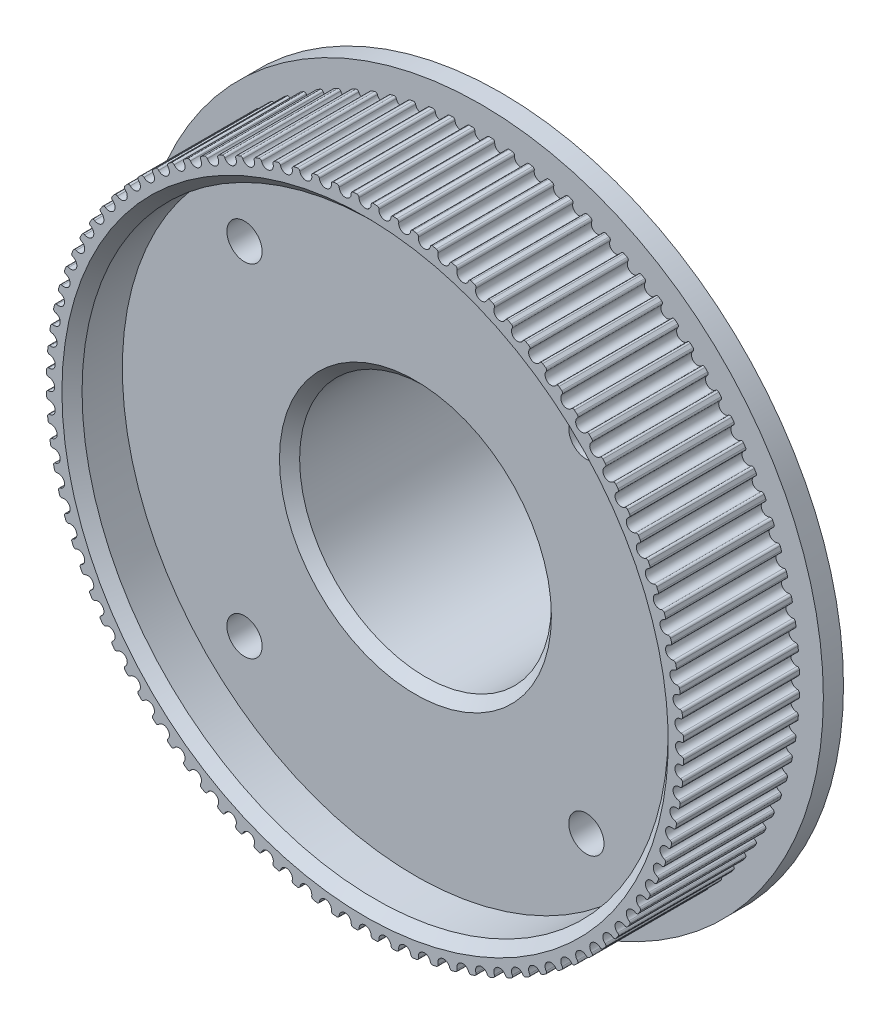
SolidWorks part; units mm, degrees
ref_plane "Спереди" through (0, 0, 0) normal (0, 0, 1) x (1, 0, 0)
ref_plane "Сверху" through (0, 0, 0) normal (0, 1, 0) x (1, 0, 0)
ref_plane "Справа" through (0, 0, 0) normal (1, 0, 0) x (0, 0, -1)
ref_axis "Ось1" through (0, 0, 55) along (0, 0, -1)
sketch "SketchRevolveGearBelt01" plane through (0, 0, 0) normal (1, 0, 0) x (0, 0, -1)
  line L0 (0, 0) -> (11.5, 0)
  line L1 (11.5, 0) -> (11.5, 31.6405)
  line L2 (11.5, 31.6405) -> (0, 31.6405)
  line L3 (0, 31.6405) -> (0, 0)
  dimension "GearBeltOutsideDiameter" = 31.6405
  dimension "D1" = 11.5
revolve "GearBelt01" add sketch "SketchRevolveGearBelt01" angle 360 about L0
sketch "SketchToothGearBelt01" plane through (0, 0, 0) normal (0, 0, 1) x (1, 0, 0)
  line L0 (-0.814, 31.63) -> (0, 34.1805)
  line L1 (0, 34.1805) -> (0.814, 31.63)
  arc A0 (0.814, 31.63) -> (0.6, 31.4215) centre (0.8086, 31.4215) ccw
  arc A1 (0.6, 31.4215) -> (-0.6, 31.4215) centre (0, 31.4215) cw
  arc A2 (-0.6, 31.4215) -> (-0.814, 31.63) centre (-0.8086, 31.4215) ccw
  dimension "GearBeltToothR1" = 0.4172
  dimension "GearBeltToothR2" = 1.2
  dimension "GearBeltToothCapX1" = 0.814
  dimension "GearBeltToothCapY1" = 2.5505
  dimension "GearBeltToothCapX2" = 0.814
  dimension "GearBeltToothCapY2" = 2.5505
extrude "ToothExtrudeCutGearBelt01" cut sketch "SketchToothGearBelt01" against normal blind 11.5
ref_axis "Ось2" through (34.8045, 0, 0) along (-1, 0, 0)
ref_plane "Плоскость1" through (0, 0, 0) normal (0, 0, -1) x (1, 0, 0)
pattern_circular "PatternGearBelt01" count 100 every 3.6 about axis through (0, 0, 55) along (0, 0, -1) of "ToothExtrudeCutGearBelt01"
sketch "Эскиз5" plane through (0, 0, -11.5) normal (0, 0, -1) x (-1, 0, 0)
  circle A0 centre (0, 0) radius 34
extrude "Бобышка-Вытянуть1" add sketch "Эскиз5" along normal blind 2
sketch "Эскиз6" plane through (0, 0, 0) normal (0, 0, 1) x (1, 0, 0)
  circle A0 centre (0, 0) radius 29.1
  dimension "D1" = 58.2
extrude "Вырез-Вытянуть2" cut sketch "Эскиз6" against normal blind 5
sketch "Эскиз7" plane through (0, 0, -13.5) normal (0, 0, -1) x (-1, 0, 0)
  circle A0 centre (0, 0) radius 20
  dimension "D1" = 40
extrude "Бобышка-Вытянуть2" add sketch "Эскиз7" along normal blind 2
sketch "Эскиз8" plane through (0, 0, -15.5) normal (0, 0, -1) x (-1, 0, 0)
  circle A0 centre (0, 0) radius 17.5
  dimension "D1" = 35
extrude "Бобышка-Вытянуть3" add sketch "Эскиз8" along normal blind 10
sketch "Эскиз9" plane through (0, 0, 0) normal (0, 0, 1) x (1, 0, 0)
  line L0 (0, 0) -> (16.9706, 16.9706) construction
  line L1 (0, 0) -> (10.5426, 0) construction
  circle A0 centre (0, 0) radius 24 construction
  circle A1 centre (16.9706, 16.9706) radius 1.75
  circle A2 centre (16.9706, 16.9706) radius 3.25
  dimension "D1" = 48
  dimension "D2" = 3.5
  dimension "D3" = 45
extrude "Вырез-Вытянуть3" cut sketch "Эскиз9" against normal through all contours A1
pattern_circular "Круговой массив2" count 4 over 360 about axis through (0, 0, -25.5) along (0, 0, 1) of "Вырез-Вытянуть3"
extrude "Вырез-Вытянуть4" cut sketch "Эскиз9<3>" against normal through all from offset 8.5 contours A2 offset against normal yes
sketch "Эскиз9<3>" plane through (0, 0, 0) normal (0, 0, 1) x (1, 0, 0) same geometry as "Эскиз9"
pattern_circular "Круговой массив3" count 4 over 360 about axis through (0, 0, -25.5) along (0, 0, 1) of "Вырез-Вытянуть4" reverse direction yes
sketch "Эскиз11" plane through (0, 0, 0) normal (0, 0, 1) x (1, 0, 0)
  circle A0 centre (0, 0) radius 12.5
extrude "Вырез-Вытянуть5" cut sketch "Эскиз11" against normal through all
chamfer "Chamfer1" distance 1 angle 45 1 edges at (29.1, 0, 0)
chamfer "Chamfer2" distance 1 angle 45 3 edges at (12.5, 0, -25.5) (-17.5, 0, -25.5) (12.5, 0, -5)
